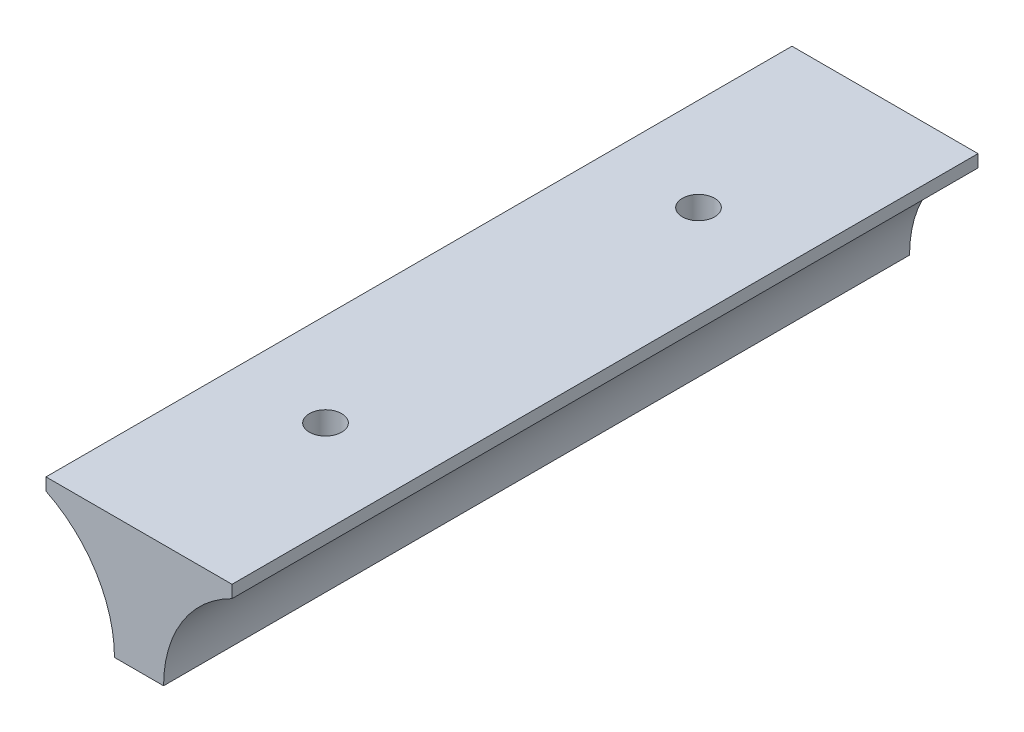
SolidWorks part; units mm, degrees
ref_plane "Front" through (0, 0, 0) normal (0, 0, 1) x (1, 0, 0)
ref_plane "Top" through (0, 0, 0) normal (0, 1, 0) x (1, 0, 0)
ref_plane "Right" through (0, 0, 0) normal (1, 0, 0) x (0, 0, -1)
sketch "Sketch1" plane through (0, 0, 0) normal (0, 0, 1) x (1, 0, 0)
  line L0 (-1.975, 0) -> (1.975, 0)
  line L1 (7.4814, 8.825) -> (7.4814, 9.825)
  line L2 (7.4814, 9.825) -> (-7.4814, 9.825)
  line L3 (-7.4814, 9.825) -> (-7.4814, 8.825)
  arc A0 (1.975, 0) -> (7.4814, 8.825) centre (11.8, 0) cw
  arc A1 (-1.975, 0) -> (-7.4814, 8.825) centre (-11.8, 0) ccw
  point P9 (0, 0)
  point P10 (0, 9.825)
  dimension "D1" = 9.825
  dimension "D2" = 9.825
  dimension "D3" = 3.95
  dimension "D4" = 1
extrude "Boss-Extrude1" add sketch "Sketch1" along normal blind 60
sketch "Sketch2" plane through (0, 9.825, 0) normal (0, 1, 0) x (1, 0, 0)
  line L0 (0, -60) -> (0, 0) construction
  line L1 (7.4814, -60) -> (-7.4814, -60) construction
  line L2 (7.4814, 0) -> (-7.4814, 0) construction
  point P6 (0, -45)
  point P7 (0, -15)
  dimension "D1" = 15
  dimension "D2" = 15
hole_wizard "Ø2.6 (2.6) Diameter Hole1" positions "3DSketch1" profile "Sketch3" hole size "Ø2.6" standard "ANSI Metric" end condition up to next
sketch3d "3DSketch1"
  point P0 (0, 9.825, 45)
  point P3 (0, 9.825, 15)
sketch "Sketch3" plane through (0, 9.825, 45) normal (1, 0, 0) x (0, 0, 1)
  line L0 (0, 0) -> (0, 9.825)
  line L1 (0, 9.825) -> (1.3, 9.825)
  line L2 (1.3, 9.825) -> (1.3, 0)
  line L5 (1.3, 0) -> (0, 0)
  line L11 (0, -6.35) -> (0, 107.95) construction
  dimension "Thru Hole Dia." = 2.6
  dimension "Thru Hole Depth" = 9.825
